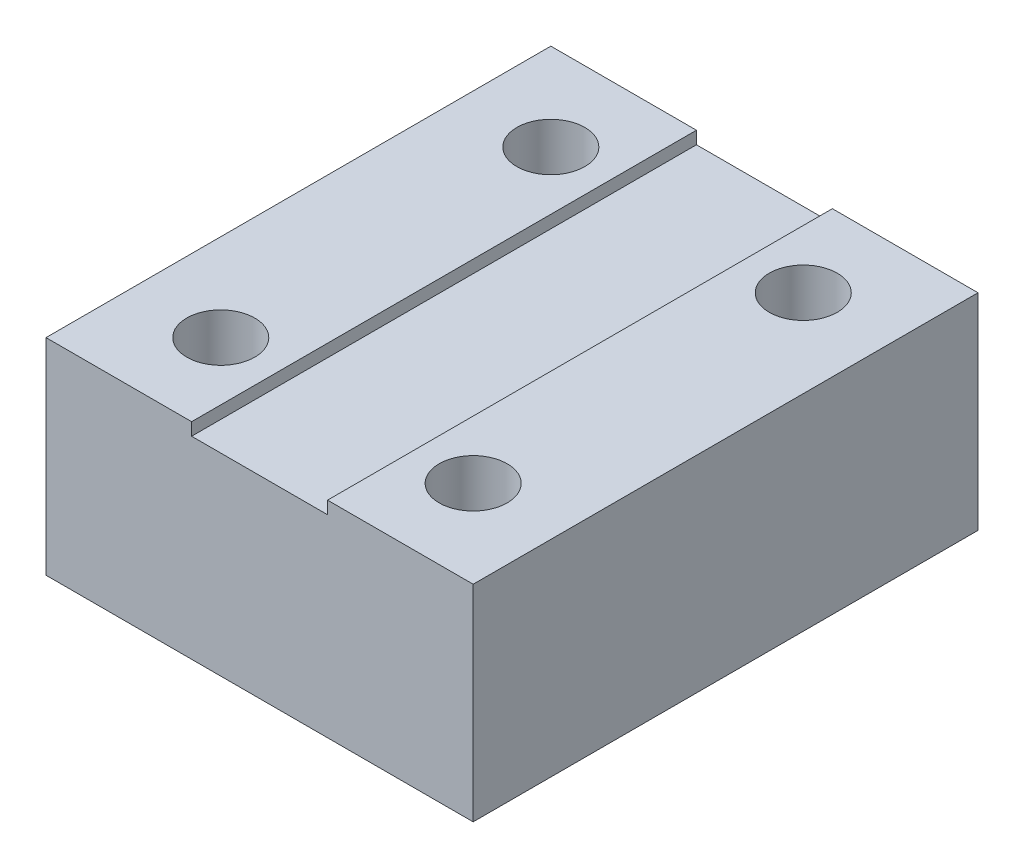
SolidWorks part; units mm, degrees
ref_plane "Piano frontale" through (0, 0, 0) normal (0, 0, 1) x (1, 0, 0)
ref_plane "Piano superiore" through (0, 0, 0) normal (0, 1, 0) x (1, 0, 0)
ref_plane "Piano destro" through (0, 0, 0) normal (1, 0, 0) x (0, 0, -1)
sketch "Schizzo1" plane through (0, 0, 0) normal (0, 0, 1) x (1, 0, 0)
  line L1 (-11, -5.3) -> (11, -5.3)
  line L2 (-11, -5.3) -> (-11, 5.3)
  line L3 (-11, 5.3) -> (11, 5.3)
  line L4 (11, -5.3) -> (11, 5.3)
  line L5 (-11, -5.3) -> (11, 5.3) construction
  line L6 (-11, 5.3) -> (11, -5.3) construction
  point P0 (0, 0)
  dimension "D1" = 22
  dimension "D2" = 10.6
extrude "Estrusione-Estrusione1" add sketch "Schizzo1" along normal mid plane 26
sketch "Schizzo5" plane through (0, 5.3, 0) normal (0, 1, 0) x (1, 0, 0)
  line L0 (11, -13) -> (11, 13) construction
  line L1 (-6.5, -8.5) -> (6.5, -8.5) construction
  line L2 (-6.5, -8.5) -> (-6.5, 8.5) construction
  line L3 (-6.5, 8.5) -> (6.5, 8.5) construction
  line L4 (6.5, -8.5) -> (6.5, 8.5) construction
  line L5 (-6.5, -8.5) -> (6.5, 8.5) construction
  line L6 (-6.5, 8.5) -> (6.5, -8.5) construction
  line L7 (11, 13) -> (-11, 13) construction
  line L10 (3.5, -13) -> (-3.5, -13)
  line L11 (3.5, -13) -> (3.5, 13)
  line L12 (3.5, 13) -> (-3.5, 13)
  line L13 (-3.5, -13) -> (-3.5, 13)
  line L14 (3.5, -13) -> (-3.5, 13) construction
  line L15 (3.5, 13) -> (-3.5, -13) construction
  circle A0 centre (6.5, 8.5) radius 1.75
  circle A1 centre (6.5, -8.5) radius 1.75
  circle A2 centre (-6.5, -8.5) radius 1.75
  circle A3 centre (-6.5, 8.5) radius 1.75
  point P0 (0, 0)
  point P12 (0, 0)
  dimension "D3" = 3.5
  dimension "D1" = 4.5
  dimension "D2" = 7
  dimension "D4" = 4.5
extrude "Taglio-Estrusione3" cut sketch "Schizzo5" against normal up to next contours A3 | A2 | A1 | A0
extrude "Taglio-Estrusione4" cut sketch "Schizzo5<3>" against normal blind 0.65 contours L13 L12 L11 L10
sketch "Schizzo5<3>" plane through (0, 5.3, 0) normal (0, 1, 0) x (1, 0, 0) same geometry as "Schizzo5"
